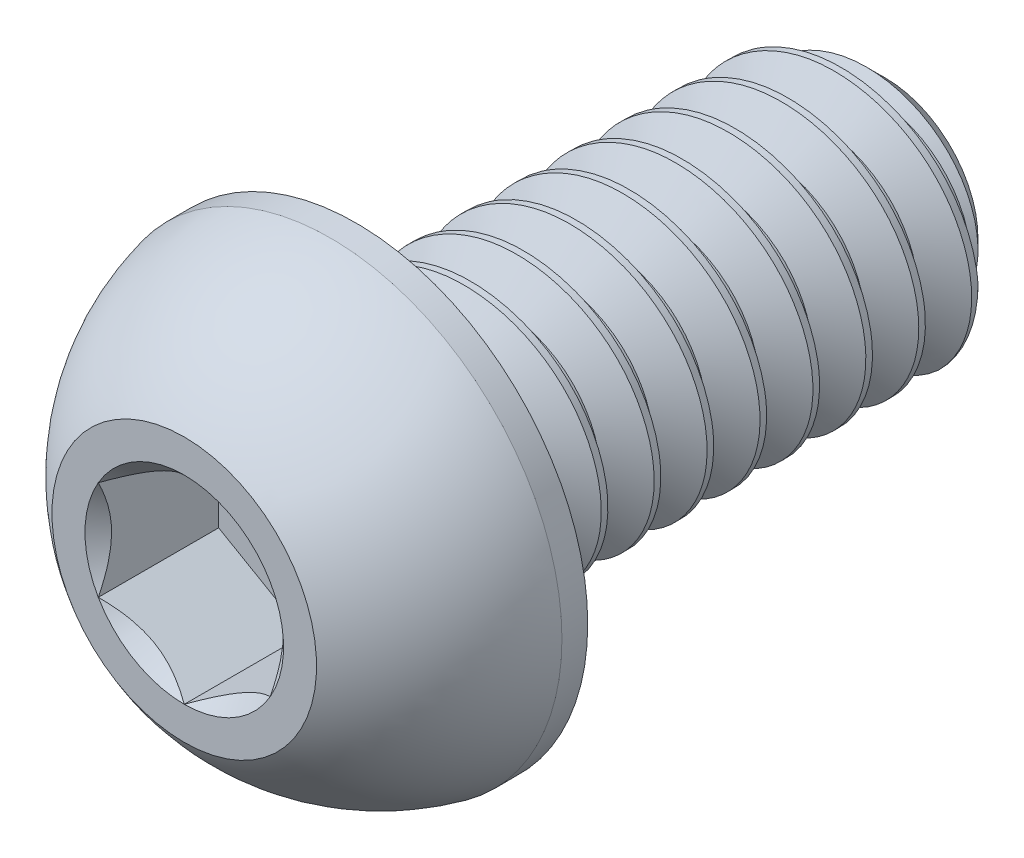
SolidWorks part; units mm, degrees
ref_plane "Front" through (0, 0, 0) normal (0, 0, 1) x (1, 0, 0)
ref_plane "Top" through (0, 0, 0) normal (0, 1, 0) x (1, 0, 0)
ref_plane "Right" through (0, 0, 0) normal (1, 0, 0) x (0, 0, -1)
sketch "Sketch1" plane through (0, 0, 0) normal (1, 0, 0) x (0, 0, -1)
  line L2 (1.3, 1) -> (5.3, 1)
  line L3 (5.3, 1) -> (5.3, 0)
  line L4 (5.3, 0) -> (1.3, 0)
  line L6 (1.105, 1.75) -> (1.3, 1.75) construction
  line L7 (5.3, 1) -> (5.3, -1) construction
  line L8 (0, 0) -> (1.3, 0) construction
  line L9 (1.3, 1.75) -> (1.3, -1.75) construction
  line L11 (1.3, 1) -> (1.3, 0)
  line L13 (0, 0.65) -> (0, -0.65) construction
  line L14 (0, 0.65) -> (0, 1) construction
  arc A3 (0, 1) -> (1.105, 1.75) centre (1.4858, 0) cw construction
  dimension "D1" = 0.195
revolve "Revolve1" add sketch "Sketch1" angle 360 mid plane about L4
sketch "Sketch3" plane through (0, 0, -5.3) normal (0, 0, -1) x (-1, 0, 0)
  circle A0 centre (0, 0) radius 1
curve "Helix/Spiral1" pitch 0.4 height 4.4 radius 1 centre (0, 0, -5.3) axis (0, 0, 1) start towards (0, 1, 0)
sketch "Sketch2" plane through (0, 0, 0) normal (1, 0, 0) x (0, 0, -1)
  line L0 (5.3, 1) -> (5.65, 1)
  line L1 (5.65, 1) -> (5.5, 0.7402)
  line L2 (5.5, 0.7402) -> (5.45, 0.7402)
  line L3 (5.45, 0.7402) -> (5.3, 1)
  line L4 (5.375, 0.8701) -> (5.575, 0.8701) construction
  dimension "D1" = 60
  dimension "D2" = 0.05
  dimension "D3" = 0.2
chamfer "Chamfer1" distance 0.3 angle 45 1 edges at (0, 1, -5.3)
sweep "Cut-Sweep1" cut profiles "Sketch2" path "Helix/Spiral1"
sketch "Sketch7" plane through (0, 0, 0) normal (1, 0, 0) x (0, 0, -1)
  line L6 (1.105, 1.75) -> (1.3, 1.75) construction
  line L8 (0, 0) -> (1.3, 0) construction
  line L11 (1.3, 1.75) -> (1.3, -1.75) construction
  line L12 (1.105, 1.75) -> (1.3, 1.75)
  line L13 (0, 0) -> (1.3, 0)
  line L14 (0, 0.65) -> (0, -0.65) construction
  line L15 (1.3, 1.75) -> (1.3, 0)
  line L16 (0, 1) -> (0, 0)
  arc A2 (1.105, 1.75) -> (0, 1) centre (1.4858, 0) ccw construction
  arc A3 (1.105, 1.75) -> (0, 1) centre (1.4858, 0) ccw
revolve "Revolve2" add sketch "Sketch7" angle 360 mid plane about L13
sketch "Sketch5" plane through (0, 0, 0) normal (0, 0, 1) x (1, 0, 0)
  line L1 (0.65, -0.3753) -> (0.65, 0.3753)
  line L2 (0.65, 0.3753) -> (0, 0.7506)
  line L3 (0, 0.7506) -> (-0.65, 0.3753)
  line L4 (-0.65, 0.3753) -> (-0.65, -0.3753)
  line L5 (-0.65, -0.3753) -> (0, -0.7506)
  line L6 (0, -0.7506) -> (0.65, -0.3753)
  circle A0 centre (0, 0) radius 0.65 construction
extrude "Cut-Extrude2" cut sketch "Sketch5" against normal blind 0.91
sketch "Sketch6" plane through (0, 0, 0) normal (0, 0, 1) x (1, 0, 0)
  circle A0 centre (0, 0) radius 0.7506
extrude "Cut-Extrude3" cut sketch "Sketch6" against normal blind 0.91 draft 45
sketch "Sketch9" [suppressed] plane through (0, 0, -4.2164) normal (0, 0, 1) x (1, 0, 0)
  circle A2 centre (0, 0) radius 3.9687
extrude "Boss-Extrude2" [suppressed] add sketch "Sketch9" against normal offset from surface (9.525 mm away) 28.575 up to face at (0, 0.7, -5.3)
sketch "Sketch10" plane through (0, 0, 0) normal (1, 0, 0) x (0, 0, -1)
  line L0 (5.3, 1) -> (5.3, -1) construction
  point P0 (4.7, -1)
  dimension "D1" = 0.6
equation "\"D3@Helix/Spiral1\" = \"Lg@Sketch1\" + \"D4@Helix/Spiral1\""
equation "\"D2@Sketch2\" = \"D4@Helix/Spiral1\" * .125"
equation "\"D3@Sketch2\" = \"D4@Helix/Spiral1\" * .5"
equation "\"D1@Chamfer1\" = \"D4@Helix/Spiral1\" * .75"
equation "\"D1@Cut-Extrude2\" = \"Head Ht@Sketch1\" * .7"
equation "\"D1@Sketch1\" = \"Head Ht@Sketch1\" * .15"
equation "\"D1@Sketch10\" = \"D4@Helix/Spiral1\" * 1.5"
equation "\"D1@Cut-Extrude3\" = \"D1@Cut-Extrude2\""
